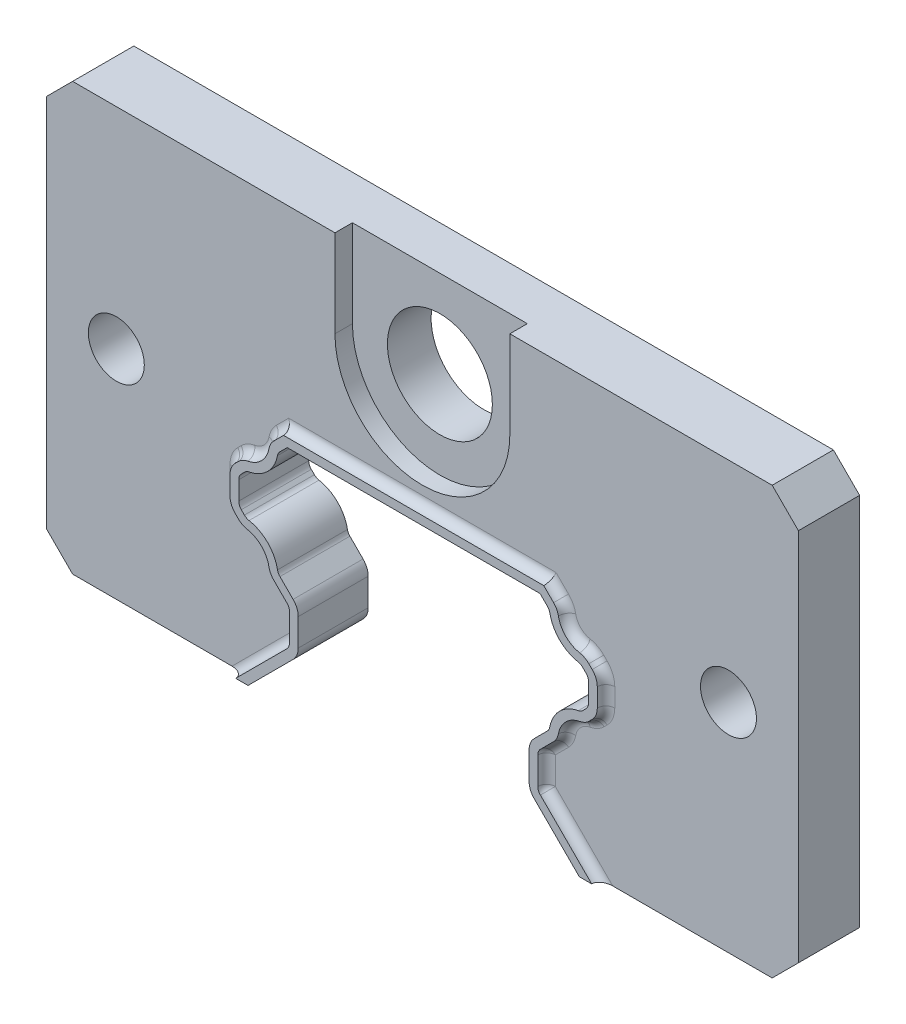
SolidWorks part; units mm, degrees
material "Plain Carbon Steel"
ref_plane "Front Plane" through (0, 0, 0) normal (0, 0, 1) x (1, 0, 0)
ref_plane "Top Plane" through (0, 0, 0) normal (0, 1, 0) x (1, 0, 0)
ref_plane "Right Plane" through (0, 0, 0) normal (1, 0, 0) x (0, 0, -1)
sketch "Sketch4" plane through (0, 0, 0) normal (0, 0, 1) x (1, 0, 0)
  line L0 (0, -1000) -> (0, 49000) construction
  line L1 (-7.2307, 12.9) -> (7.2307, 12.9)
  line L2 (19.9999, 0) -> (9.4707, 0)
  line L3 (21.5, 1.5) -> (19.9999, 0)
  line L4 (21.5, 22.9) -> (21.5, 1.5)
  line L5 (-21.5, 1.5) -> (-21.5, 22.8998)
  line L6 (-19.9999, 0) -> (-21.5, 1.5)
  line L7 (-9.4707, 0) -> (-19.9999, 0)
  line L8 (-7.6477, 12.483) -> (-7.2307, 12.9)
  line L9 (-9.8536, 10.2772) -> (-9.6633, 10.4674)
  line L10 (-10, 8.8664) -> (-10, 9.9236)
  line L11 (-9.6753, 8.3346) -> (-9.8536, 8.5128)
  line L12 (-6.8929, 5.5522) -> (-7.6454, 6.3047)
  line L13 (-6.6, 3.2849) -> (-6.6, 4.8451)
  line L14 (-9.4707, 0) -> (-6.8929, 2.5778)
  line L15 (6.8929, 2.5778) -> (9.4707, 0)
  line L16 (6.6, 4.8451) -> (6.6, 3.2849)
  line L17 (7.6454, 6.3047) -> (6.8929, 5.5522)
  line L18 (9.8536, 8.5128) -> (9.6753, 8.3346)
  line L19 (10, 9.9236) -> (10, 8.8664)
  line L20 (9.6633, 10.4674) -> (9.8536, 10.2772)
  line L21 (7.2307, 12.9) -> (7.6477, 12.483)
  line L22 (18.7501, 9.9) -> (18.7501, 14.9) construction
  line L23 (16.2501, 12.4) -> (21.2501, 12.4) construction
  line L24 (-18.7501, 9.9) -> (-18.7501, 14.9) construction
  line L25 (-21.2499, 12.4) -> (-16.2499, 12.4) construction
  line L27 (20.0001, 24.4) -> (21.5, 22.9)
  line L28 (-19.9999, 24.4) -> (20.0001, 24.4)
  line L29 (-21.5, 22.8998) -> (-19.9999, 24.4)
  arc A0 (-7.6477, 12.483) -> (-7.7854, 12.2224) centre (-7.2941, 12.1295) ccw
  arc A1 (-9.4027, 10.6051) -> (-7.7854, 12.2224) centre (-9.78, 12.5997) ccw
  arc A2 (-9.4027, 10.6051) -> (-9.6633, 10.4674) centre (-9.3098, 10.1138) ccw
  arc A3 (-9.8536, 10.2772) -> (-10, 9.9236) centre (-9.5, 9.9236) ccw
  arc A4 (-10, 8.8664) -> (-9.8536, 8.5128) centre (-9.5, 8.8664) ccw
  arc A5 (-9.6753, 8.3346) -> (-9.4124, 8.1964) centre (-9.3218, 8.6882) ccw
  arc A6 (-7.7836, 6.5677) -> (-9.4124, 8.1964) centre (-9.78, 6.2) ccw
  arc A7 (-7.7836, 6.5677) -> (-7.6454, 6.3047) centre (-7.2919, 6.6583) ccw
  arc A8 (-6.6, 4.8451) -> (-6.8929, 5.5522) centre (-7.6, 4.8451) ccw
  arc A9 (-6.8929, 2.5778) -> (-6.6, 3.2849) centre (-7.6, 3.2849) ccw
  arc A10 (6.6, 3.2849) -> (6.8929, 2.5778) centre (7.6, 3.2849) ccw
  arc A11 (6.8929, 5.5522) -> (6.6, 4.8451) centre (7.6, 4.8451) ccw
  arc A12 (7.6454, 6.3047) -> (7.7836, 6.5677) centre (7.2919, 6.6583) ccw
  arc A13 (9.4124, 8.1964) -> (9.6753, 8.3346) centre (9.3218, 8.6882) ccw
  arc A14 (9.4124, 8.1964) -> (7.7836, 6.5677) centre (9.78, 6.2) ccw
  arc A15 (9.8536, 8.5128) -> (10, 8.8664) centre (9.5, 8.8664) ccw
  arc A16 (10, 9.9236) -> (9.8536, 10.2772) centre (9.5, 9.9236) ccw
  arc A17 (9.6633, 10.4674) -> (9.4027, 10.6051) centre (9.3098, 10.1138) ccw
  arc A18 (7.7854, 12.2224) -> (9.4027, 10.6051) centre (9.78, 12.5997) ccw
  arc A19 (7.7854, 12.2224) -> (7.6477, 12.483) centre (7.2941, 12.1295) ccw
  point P37 (0, 12.9)
  dimension "D1" = 24.4
  dimension "D2" = 20
  dimension "D3" = 13.2
  dimension "D4" = 43
  dimension "D5" = 12.9
extrude "Endseal 1" add sketch "Sketch4" along normal blind 3.5 separate body
sketch "Sketch6" plane through (0, 0, 3.5) normal (0, 0, 1) x (1, 0, 0)
  line L0 (-10.1778, 0) -> (-7.2464, 2.9314)
  line L1 (-7.1, 3.2849) -> (-7.1, 4.8451)
  line L2 (-7.2464, 5.1986) -> (-7.999, 5.9512)
  line L3 (-10.0289, 7.9811) -> (-10.2071, 8.1593)
  line L4 (-10.5, 8.8664) -> (-10.5, 9.9236)
  line L5 (-10.2071, 10.6307) -> (-10.0169, 10.8209)
  line L6 (-8.0012, 12.8366) -> (-7.4378, 13.4)
  line L7 (-7.4378, 13.4) -> (7.4378, 13.4)
  line L8 (7.4378, 13.4) -> (8.0012, 12.8366)
  line L9 (10.0169, 10.8209) -> (10.2071, 10.6307)
  line L10 (10.5, 9.9236) -> (10.5, 8.8664)
  line L11 (10.2071, 8.1593) -> (10.0289, 7.9811)
  line L12 (7.999, 5.9512) -> (7.2464, 5.1986)
  line L13 (7.1, 4.8451) -> (7.1, 3.2849)
  line L14 (7.2464, 2.9314) -> (10.1778, 0)
  line L15 (-7.2307, 12.9) -> (7.2307, 12.9) construction
  line L16 (7.2307, 12.9) -> (7.6477, 12.483) construction
  line L17 (9.6633, 10.4674) -> (9.8536, 10.2772) construction
  line L18 (10, 9.9236) -> (10, 8.8664) construction
  line L19 (9.8536, 8.5128) -> (9.6753, 8.3346) construction
  line L20 (7.6454, 6.3047) -> (6.8929, 5.5522) construction
  line L21 (6.6, 4.8451) -> (6.6, 3.2849) construction
  line L22 (6.8929, 2.5778) -> (9.4707, 0) construction
  line L23 (-7.6477, 12.483) -> (-7.2307, 12.9) construction
  line L24 (-9.8536, 10.2772) -> (-9.6633, 10.4674) construction
  line L25 (-10, 8.8664) -> (-10, 9.9236) construction
  line L26 (-9.6753, 8.3346) -> (-9.8536, 8.5128) construction
  line L27 (-6.8929, 5.5522) -> (-7.6454, 6.3047) construction
  line L28 (-6.6, 3.2849) -> (-6.6, 4.8451) construction
  line L29 (-9.4707, 0) -> (-6.8929, 2.5778) construction
  line L30 (-7.2307, 12.9) -> (7.2307, 12.9)
  line L31 (7.2307, 12.9) -> (7.6477, 12.483)
  line L32 (9.6633, 10.4674) -> (9.8536, 10.2772)
  line L33 (10, 9.9236) -> (10, 8.8664)
  line L34 (9.8536, 8.5128) -> (9.6753, 8.3346)
  line L35 (7.6454, 6.3047) -> (6.8929, 5.5522)
  line L36 (6.6, 4.8451) -> (6.6, 3.2849)
  line L37 (6.8929, 2.5778) -> (9.4707, 0)
  line L38 (-7.6477, 12.483) -> (-7.2307, 12.9)
  line L39 (-9.8536, 10.2772) -> (-9.6633, 10.4674)
  line L40 (-10, 8.8664) -> (-10, 9.9236)
  line L41 (-9.6753, 8.3346) -> (-9.8536, 8.5128)
  line L42 (-6.8929, 5.5522) -> (-7.6454, 6.3047)
  line L43 (-6.6, 3.2849) -> (-6.6, 4.8451)
  line L44 (-9.4707, 0) -> (-6.8929, 2.5778)
  line L45 (9.4707, 0) -> (10.1778, 0)
  line L47 (-9.4707, 0) -> (-10.1778, 0)
  line L49 (-9.8243, 0.3536) -> (-7.2464, 2.9314) construction
  line L50 (7.2464, 2.9314) -> (9.8243, 0.3536) construction
  arc A0 (-7.2464, 2.9314) -> (-7.1, 3.2849) centre (-7.6, 3.2849) ccw
  arc A1 (-7.1, 4.8451) -> (-7.2464, 5.1986) centre (-7.6, 4.8451) ccw
  arc A2 (-8.2753, 6.4771) -> (-7.999, 5.9512) centre (-7.2919, 6.6583) ccw
  arc A3 (-8.2753, 6.4771) -> (-9.5029, 7.7047) centre (-9.78, 6.2) ccw
  arc A4 (7.7854, 12.2224) -> (7.6477, 12.483) centre (7.2941, 12.1295) ccw construction
  arc A5 (7.7854, 12.2224) -> (9.4027, 10.6051) centre (9.78, 12.5997) ccw construction
  arc A6 (9.6633, 10.4674) -> (9.4027, 10.6051) centre (9.3098, 10.1138) ccw construction
  arc A7 (10, 9.9236) -> (9.8536, 10.2772) centre (9.5, 9.9236) ccw construction
  arc A8 (9.8536, 8.5128) -> (10, 8.8664) centre (9.5, 8.8664) ccw construction
  arc A9 (9.4124, 8.1964) -> (9.6753, 8.3346) centre (9.3218, 8.6882) ccw construction
  arc A10 (9.4124, 8.1964) -> (7.7836, 6.5677) centre (9.78, 6.2) ccw construction
  arc A11 (7.6454, 6.3047) -> (7.7836, 6.5677) centre (7.2919, 6.6583) ccw construction
  arc A12 (6.8929, 5.5522) -> (6.6, 4.8451) centre (7.6, 4.8451) ccw construction
  arc A13 (6.6, 3.2849) -> (6.8929, 2.5778) centre (7.6, 3.2849) ccw construction
  arc A14 (-7.6477, 12.483) -> (-7.7854, 12.2224) centre (-7.2941, 12.1295) ccw construction
  arc A15 (-9.4027, 10.6051) -> (-7.7854, 12.2224) centre (-9.78, 12.5997) ccw construction
  arc A16 (-9.4027, 10.6051) -> (-9.6633, 10.4674) centre (-9.3098, 10.1138) ccw construction
  arc A17 (-9.8536, 10.2772) -> (-10, 9.9236) centre (-9.5, 9.9236) ccw construction
  arc A18 (-10, 8.8664) -> (-9.8536, 8.5128) centre (-9.5, 8.8664) ccw construction
  arc A19 (-9.6753, 8.3346) -> (-9.4124, 8.1964) centre (-9.3218, 8.6882) ccw construction
  arc A20 (-7.7836, 6.5677) -> (-9.4124, 8.1964) centre (-9.78, 6.2) ccw construction
  arc A21 (-7.7836, 6.5677) -> (-7.6454, 6.3047) centre (-7.2919, 6.6583) ccw construction
  arc A22 (-6.6, 4.8451) -> (-6.8929, 5.5522) centre (-7.6, 4.8451) ccw construction
  arc A23 (-6.8929, 2.5778) -> (-6.6, 3.2849) centre (-7.6, 3.2849) ccw construction
  arc A24 (7.7854, 12.2224) -> (7.6477, 12.483) centre (7.2941, 12.1295) ccw
  arc A25 (7.7854, 12.2224) -> (9.4027, 10.6051) centre (9.78, 12.5997) ccw
  arc A26 (9.6633, 10.4674) -> (9.4027, 10.6051) centre (9.3098, 10.1138) ccw
  arc A27 (10, 9.9236) -> (9.8536, 10.2772) centre (9.5, 9.9236) ccw
  arc A28 (9.8536, 8.5128) -> (10, 8.8664) centre (9.5, 8.8664) ccw
  arc A29 (9.4124, 8.1964) -> (9.6753, 8.3346) centre (9.3218, 8.6882) ccw
  arc A30 (9.4124, 8.1964) -> (7.7836, 6.5677) centre (9.78, 6.2) ccw
  arc A31 (7.6454, 6.3047) -> (7.7836, 6.5677) centre (7.2919, 6.6583) ccw
  arc A32 (6.8929, 5.5522) -> (6.6, 4.8451) centre (7.6, 4.8451) ccw
  arc A33 (6.6, 3.2849) -> (6.8929, 2.5778) centre (7.6, 3.2849) ccw
  arc A34 (-7.6477, 12.483) -> (-7.7854, 12.2224) centre (-7.2941, 12.1295) ccw
  arc A35 (-9.4027, 10.6051) -> (-7.7854, 12.2224) centre (-9.78, 12.5997) ccw
  arc A36 (-9.4027, 10.6051) -> (-9.6633, 10.4674) centre (-9.3098, 10.1138) ccw
  arc A37 (-9.8536, 10.2772) -> (-10, 9.9236) centre (-9.5, 9.9236) ccw
  arc A38 (-10, 8.8664) -> (-9.8536, 8.5128) centre (-9.5, 8.8664) ccw
  arc A39 (-9.6753, 8.3346) -> (-9.4124, 8.1964) centre (-9.3218, 8.6882) ccw
  arc A40 (-7.7836, 6.5677) -> (-9.4124, 8.1964) centre (-9.78, 6.2) ccw
  arc A41 (-7.7836, 6.5677) -> (-7.6454, 6.3047) centre (-7.2919, 6.6583) ccw
  arc A42 (-6.6, 4.8451) -> (-6.8929, 5.5522) centre (-7.6, 4.8451) ccw
  arc A43 (-6.8929, 2.5778) -> (-6.6, 3.2849) centre (-7.6, 3.2849) ccw
  arc A44 (-10.0289, 7.9811) -> (-9.5029, 7.7047) centre (-9.3218, 8.6882) ccw
  arc A45 (-10.5, 8.8664) -> (-10.2071, 8.1593) centre (-9.5, 8.8664) ccw
  arc A46 (-10.2071, 10.6307) -> (-10.5, 9.9236) centre (-9.5, 9.9236) ccw
  arc A47 (-9.4957, 11.0964) -> (-10.0169, 10.8209) centre (-9.3098, 10.1138) ccw
  arc A48 (-9.4957, 11.0964) -> (-8.2767, 12.3154) centre (-9.78, 12.5997) ccw
  arc A49 (-8.0012, 12.8366) -> (-8.2767, 12.3154) centre (-7.2941, 12.1295) ccw
  arc A50 (8.2767, 12.3154) -> (8.0012, 12.8366) centre (7.2941, 12.1295) ccw
  arc A51 (8.2767, 12.3154) -> (9.4957, 11.0964) centre (9.78, 12.5997) ccw
  arc A52 (10.0169, 10.8209) -> (9.4957, 11.0964) centre (9.3098, 10.1138) ccw
  arc A53 (10.5, 9.9236) -> (10.2071, 10.6307) centre (9.5, 9.9236) ccw
  arc A54 (10.2071, 8.1593) -> (10.5, 8.8664) centre (9.5, 8.8664) ccw
  arc A55 (9.5029, 7.7047) -> (10.0289, 7.9811) centre (9.3218, 8.6882) ccw
  arc A56 (9.5029, 7.7047) -> (8.2753, 6.4771) centre (9.78, 6.2) ccw
  arc A57 (7.999, 5.9512) -> (8.2753, 6.4771) centre (7.2919, 6.6583) ccw
  arc A58 (7.2464, 5.1986) -> (7.1, 4.8451) centre (7.6, 4.8451) ccw
  arc A59 (7.1, 3.2849) -> (7.2464, 2.9314) centre (7.6, 3.2849) ccw
  dimension "D1" = 0.5
extrude "Boss-Extrude1" add sketch "Sketch6" along normal blind 0.5
fillet "Fillet1" radius 0.5 35 edges at (-7.7195, 13.1183, 3.5) (-8.1782, 12.5967, 3.5) (-8.6982, 11.5179, 3.5) (-9.777, 10.9979, 3.5) (-10.112, 10.7258, 3.5) (-10.4239, 10.3063, 3.5) (-10.5, 9.395, 3.5) (-10.4239, 8.4837, 3.5) (-10.118, 8.0702, 3.5) (-9.7869, 7.8029, 3.5) (-8.6982, 7.2819, 3.5) (-8.1771, 6.1932, 3.5) (-7.6227, 5.5749, 3.5) (-7.1381, 5.0364, 3.5) (-7.1, 4.065, 3.5) (-7.1381, 3.0936, 3.5) (7.7195, 13.1183, 3.5) (8.1782, 12.5967, 3.5) (8.6982, 11.5179, 3.5) (9.777, 10.9979, 3.5) (10.112, 10.7258, 3.5) (10.4239, 10.3063, 3.5) (10.5, 9.395, 3.5) (10.4239, 8.4837, 3.5) (10.118, 8.0702, 3.5) (9.7869, 7.8029, 3.5) (8.6982, 7.2819, 3.5) (8.1771, 6.1932, 3.5) (7.6227, 5.5749, 3.5) (7.1381, 5.0364, 3.5) (7.1, 4.065, 3.5) (7.1381, 3.0936, 3.5) (-8.7121, 1.4657, 3.5) (0, 13.4, 3.5) (8.7121, 1.4657, 3.5)
hole_wizard "Ø6.0 (6) Diameter Hole1" positions "Sketch8" profile "Sketch7" hole size "Ø6.0" standard "ANSI Metric"
sketch "Sketch8" plane through (0, 0, 3.5) normal (0, 0, 1) x (1, 0, 0)
  line L1 (20.0001, 24.4) -> (-19.9999, 24.4) construction
  line L2 (0, -1000) -> (0, 49000) construction
  point P0 (0, 19.4)
  dimension "D1" = 5
sketch "Sketch7" plane through (0, 19.4, 3.5) normal (1, 0, 0) x (0, -1, 0)
  line L0 (0, 0) -> (0, 14.0617)
  line L1 (0, 14.0617) -> (3, 12.5)
  line L2 (3, 12.5) -> (3, 0)
  line L5 (3, 0) -> (0, 0)
  line L10 (0, 14.0617) -> (-3, 12.5) construction
  line L11 (0, -6.35) -> (0, 107.95) construction
  dimension "Hole Dia." = 6
  dimension "Hole Depth" = 12.5
  dimension "Drill Angle" = 125
sketch "Sketch9" plane through (0, 0, 3.5) normal (0, 0, 1) x (1, 0, 0)
  line L0 (5, 19.4) -> (5, 35)
  line L2 (5, 35) -> (-5, 35)
  line L3 (-5, 35) -> (-5, 19.4)
  arc A0 (-5, 19.4) -> (5, 19.4) centre (0, 19.4) ccw
  dimension "D1" = 10
extrude "Cut-Extrude2" cut sketch "Sketch9" against normal blind 1
hole_wizard "Ø3.2 (3.2) Diameter Hole1" positions "Sketch11" profile "Sketch10" hole size "Ø3.2" standard "ANSI Metric" end condition through all
sketch "Sketch11" plane through (0, 0, 3.5) normal (0, 0, 1) x (1, 0, 0)
  line L0 (0, -1000) -> (0, 49000) construction
  line L2 (-5, 24.4) -> (-19.9999, 24.4) construction
  point P0 (-17.5, 12.4)
  point P2 (17.5, 12.4)
  dimension "D1" = 35
  dimension "D2" = 12
sketch "Sketch10" plane through (-17.5, 12.4, 3.5) normal (1, 0, 0) x (0, -1, 0)
  line L0 (0, 0) -> (0, 3.5)
  line L1 (0, 3.5) -> (1.6, 3.5)
  line L2 (1.6, 3.5) -> (1.6, 0)
  line L5 (1.6, 0) -> (0, 0)
  line L11 (0, -6.35) -> (0, 107.95) construction
  dimension "Thru Hole Dia." = 3.2
  dimension "Thru Hole Depth" = 3.5
